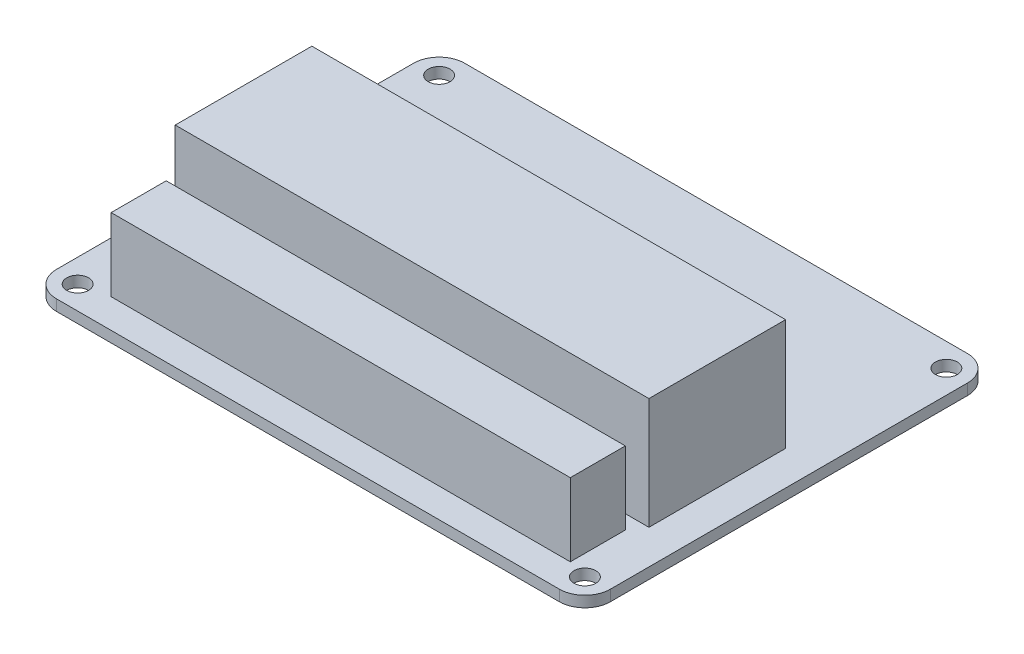
SolidWorks part; units mm, degrees
ref_plane "Front Plane" through (0, 0, 0) normal (0, 0, 1) x (1, 0, 0)
ref_plane "Top Plane" through (0, 0, 0) normal (0, 1, 0) x (1, 0, 0)
ref_plane "Right Plane" through (0, 0, 0) normal (1, 0, 0) x (0, 0, -1)
sketch "Sketch1" plane through (0, 0, 0) normal (0, 1, 0) x (1, 0, 0)
  line L0 (76, -28) -> (72.8, -28)
  line L1 (76, 0) -> (0, 0)
  line L2 (76, 0) -> (76, -56)
  line L3 (76, -56) -> (0, -56)
  line L4 (0, 0) -> (0, -56)
  line L5 (76, 0) -> (0, -56) construction
  line L6 (76, -56) -> (0, 0) construction
  line L7 (72.8, -52.8) -> (72.8, -3.2)
  line L8 (38, -56) -> (38, 0)
  line L9 (38, -56) -> (38, -51.9)
  circle A0 centre (72.8, -52.8) radius 1.5
  circle A1 centre (72.8, -3.2) radius 1.5
  circle A2 centre (3.2, -3.2) radius 1.5
  circle A3 centre (3.2, -52.8) radius 1.5
  point P0 (38, -28)
  point P10 (72.8, -28)
  point P20 (0, 0)
  dimension "D3" = 3.2
  dimension "D1" = 76
  dimension "D2" = 56
  dimension "D4" = 4.1
extrude "Boss-Extrude1" add sketch "Sketch1" along normal blind 1.5 contours A1 L2 L1 L8 L3 A0 | L3 L8 L1 L4 A2 A3 region at (56.8943, 0, 28) region at (19.1057, 0, 28)
fillet "Fillet1" radius 3.5 4 edges at (76, 0.75, 0) (76, 0.75, 56) (0, 0.75, 56) (0, 0.75, 0)
sketch "Sketch3" plane through (0, 1.5, 0) normal (0, 1, 0) x (1, 0, 0)
  line L1 (76, -56) -> (70, -56)
  line L2 (76, -56) -> (76, -52)
  line L3 (76, -52) -> (70, -52)
  line L4 (70, -56) -> (70, -52)
  line L5 (70, -52) -> (7, -52)
  line L6 (70, -52) -> (70, -44.45)
  line L7 (70, -44.45) -> (7, -44.45)
  line L8 (7, -52) -> (7, -44.45)
  dimension "D1" = 6
  dimension "D2" = 4
  dimension "D3" = 63
  dimension "D4" = 7.55
extrude "Boss-Extrude3" add sketch "Sketch3" along normal blind 10 contours L8 L5 L6 L7 region at (38.5, 1.5, 48.225)
sketch "Sketch4" plane through (0, 1.5, 0) normal (0, 1, 0) x (1, 0, 0)
  line L1 (76.0141, -56.0054) -> (71.2941, -56.0054)
  line L2 (76.0141, -56.0054) -> (76.0141, -42.5054)
  line L3 (76.0141, -42.5054) -> (71.2941, -42.5054)
  line L4 (71.2941, -56.0054) -> (71.2941, -42.5054)
  line L5 (71.2941, -42.5054) -> (6.2941, -42.5054)
  line L6 (71.2941, -42.5054) -> (71.2941, -23.7554)
  line L7 (71.2941, -23.7554) -> (6.2941, -23.7554)
  line L8 (6.2941, -42.5054) -> (6.2941, -23.7554)
  point P0 (0, 0)
  dimension "D1" = 4.72
  dimension "D2" = 13.5
  dimension "D3" = 65
  dimension "D4" = 18.75
extrude "Boss-Extrude4" add sketch "Sketch4" along normal blind 15.3 contours L8 L5 L6 L7 region at (38.7941, 1.5, 33.1304)
